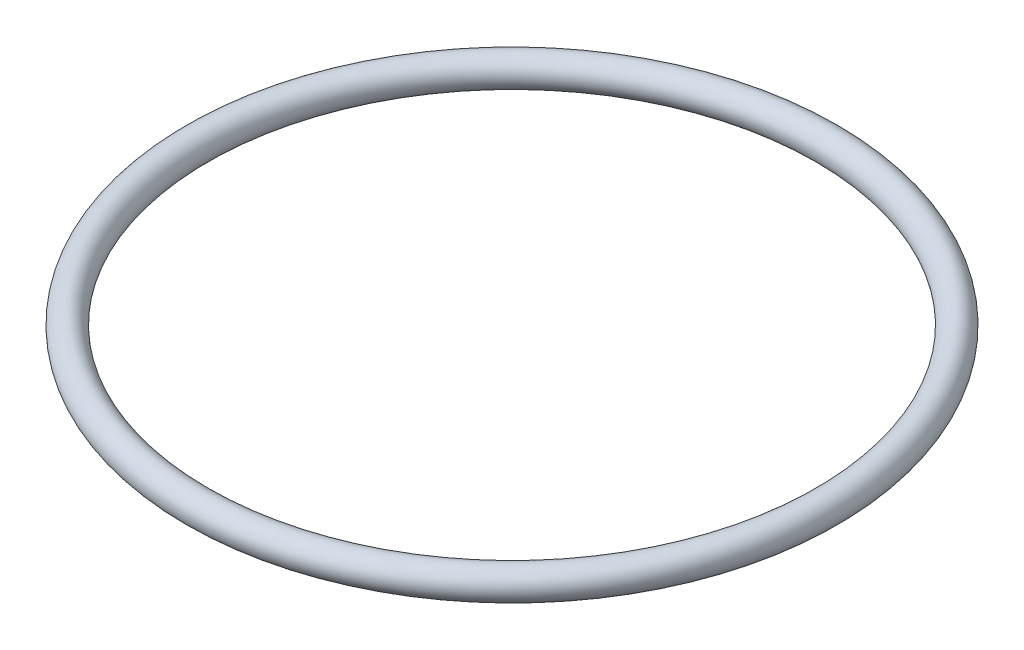
SolidWorks part; units mm, degrees
material "Rubber"
ref_plane "Front Plane" through (0, 0, 0) normal (0, 0, 1) x (1, 0, 0)
ref_plane "Top Plane" through (0, 0, 0) normal (0, 1, 0) x (1, 0, 0)
ref_plane "Right Plane" through (0, 0, 0) normal (1, 0, 0) x (0, 0, -1)
sketch "Sketch1" plane through (0, 0, 0) normal (0, 0, 1) x (1, 0, 0)
  line L0 (0, -3.4925) -> (0, 3.4925) construction
  circle A1 centre (-73.025, 0) radius 3.4925
  point P3 (-69.5325, 0)
  point P4 (-76.5175, 0)
  point P6 (0, 0)
  dimension "D2" = 139.065
  dimension "D1" = 6.985
  dimension "D3" = 153.035
revolve "Revolve1" add sketch "Sketch1" angle 360 about L0
sketch "Profile Center" plane through (0, 0, 0) normal (0, 1, 0) x (1, 0, 0)
  circle A0 centre (0, 0) radius 50.8 construction
  dimension "D1" = 101.6
